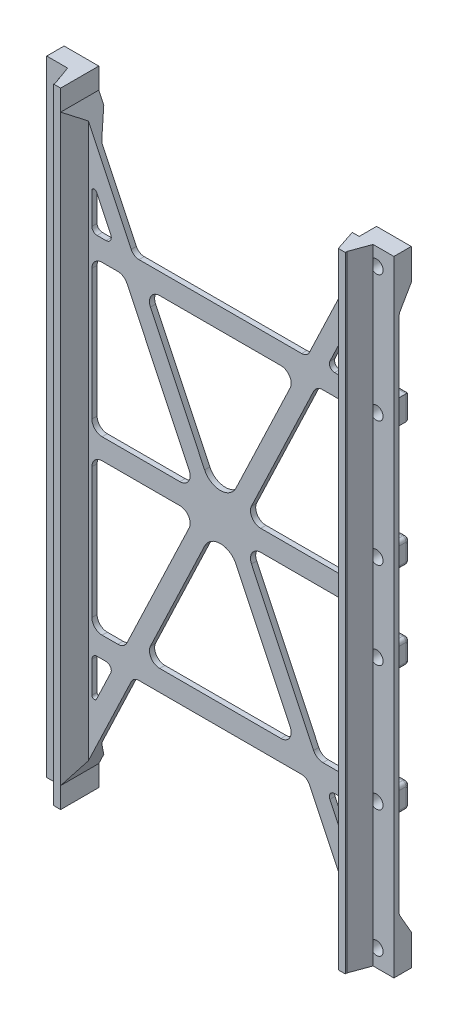
SolidWorks part; units mm, degrees
ref_plane "Front Plane" through (0, 0, 0) normal (0, 0, 1) x (1, 0, 0)
ref_plane "Top Plane" through (0, 0, 0) normal (0, 1, 0) x (1, 0, 0)
ref_plane "Right Plane" through (0, 0, 0) normal (1, 0, 0) x (0, 0, -1)
sketch "Sketch1" plane through (0, 0, 0) normal (0, 0, 1) x (1, 0, 0)
  line L0 (-40, 90) -> (-40, 84)
  line L4 (-50, -90) -> (-50, 90)
  line L5 (-45, 90) -> (-45, -90) construction
  line L6 (-50, -52.5) -> (-30.538, -52.5) construction
  line L7 (-50, 52.5) -> (-30.538, 52.5) construction
  line L8 (-40, 84) -> (-25.6787, 53.9252)
  line L9 (0, 90) -> (0, -90) construction
  line L10 (-50, 0) -> (50, 0) construction
  line L11 (-35.5, 52.5) -> (-32.9136, 52.5)
  line L12 (-40, 90) -> (-50, 90)
  line L13 (-35.668, 63.2731) -> (-31.5593, 54.6449)
  line L14 (-37, -5.95) -> (-37, -43.55)
  line L15 (-34.05, 46.5) -> (-29.5434, 46.5)
  line L16 (-25, 46.5) -> (0, 46.5) construction
  line L17 (-44.5143, 81.8503) -> (-29.5143, 50.3503) construction
  line L18 (-25, 52.5) -> (0, 52.5) construction
  line L19 (-34.05, -3) -> (-11.6387, -3)
  line L20 (-37, 54) -> (-37, 62.9721)
  line L21 (-26.88, 44.8183) -> (-8.9752, 7.2183)
  line L22 (-23.4215, 52.5) -> (23.4215, 52.5)
  line L23 (-40, 84) -> (-25, 52.5) construction
  line L24 (-20.1341, 42.2817) -> (-4.5143, 9.48)
  line L25 (-17.4707, 46.5) -> (17.4707, 46.5)
  line L26 (-17.4707, -46.5) -> (17.4707, -46.5)
  line L27 (-34.05, 3) -> (-11.6387, 3)
  line L28 (-50, 3) -> (50, 3) construction
  line L29 (-37, 5.95) -> (-37, 43.55)
  line L30 (-20.1341, -42.2817) -> (-4.5143, -9.48)
  line L31 (-23.4215, -52.5) -> (23.4215, -52.5)
  line L32 (-26.88, -44.8183) -> (-8.9752, -7.2183)
  line L33 (-37, -54) -> (-37, -62.9721)
  line L34 (-34.05, -46.5) -> (-29.5434, -46.5)
  line L35 (-35.668, -63.2731) -> (-31.5593, -54.6449)
  line L36 (-40, -90) -> (-50, -90)
  line L37 (-35.5, -52.5) -> (-32.9136, -52.5)
  line L38 (-40, -84) -> (-25.6787, -53.9252)
  line L39 (-40, -90) -> (-40, -84)
  line L40 (50, 0) -> (-50, 0) construction
  line L41 (50, 52.5) -> (30.538, 52.5) construction
  line L42 (50, -52.5) -> (30.538, -52.5) construction
  line L43 (45, 90) -> (45, -90) construction
  line L44 (40, -90) -> (40, -84)
  line L45 (40, -84) -> (25.6787, -53.9252)
  line L46 (35.5, -52.5) -> (32.9136, -52.5)
  line L47 (40, -90) -> (50, -90)
  line L48 (35.668, -63.2731) -> (31.5593, -54.6449)
  line L49 (34.05, -46.5) -> (29.5434, -46.5)
  line L50 (37, -54) -> (37, -62.9721)
  line L51 (26.88, -44.8183) -> (8.9752, -7.2183)
  line L52 (20.1341, -42.2817) -> (4.5143, -9.48)
  line L53 (37, 5.95) -> (37, 43.55)
  line L54 (34.05, 3) -> (11.6387, 3)
  line L55 (20.1341, 42.2817) -> (4.5143, 9.48)
  line L56 (26.88, 44.8183) -> (8.9752, 7.2183)
  line L57 (37, 54) -> (37, 62.9721)
  line L58 (34.05, -3) -> (11.6387, -3)
  line L59 (34.05, 46.5) -> (29.5434, 46.5)
  line L60 (37, -5.95) -> (37, -43.55)
  line L61 (35.668, 63.2731) -> (31.5593, 54.6449)
  line L62 (40, 90) -> (50, 90)
  line L63 (35.5, 52.5) -> (32.9136, 52.5)
  line L64 (40, 84) -> (25.6787, 53.9252)
  line L65 (50, -90) -> (50, 90)
  line L66 (40, 90) -> (40, 84)
  arc A0 (-35.668, 63.2731) -> (-37, 62.9721) centre (-36.3, 62.9721) ccw
  arc A1 (-31.5593, 54.6449) -> (-32.9136, 52.5) centre (-32.9136, 54) cw
  arc A2 (-35.5, 52.5) -> (-37, 54) centre (-35.5, 54) cw
  arc A3 (-11.6387, 3) -> (-8.9752, 7.2183) centre (-11.6387, 5.95) ccw
  arc A4 (-34.05, 3) -> (-37, 5.95) centre (-34.05, 5.95) cw
  arc A5 (-26.88, 44.8183) -> (-29.5434, 46.5) centre (-29.5434, 43.55) ccw
  arc A6 (-34.05, 46.5) -> (-37, 43.55) centre (-34.05, 43.55) ccw
  arc A7 (-23.4215, 52.5) -> (-25.6787, 53.9252) centre (-23.4215, 55) cw
  arc A8 (-20.1341, 42.2817) -> (-17.4707, 46.5) centre (-17.4707, 43.55) cw
  circle A9 centre (-45, 85) radius 1.8844
  circle A10 centre (-45, 48.5) radius 1.8844
  circle A11 centre (-45, 12.5) radius 1.8844
  circle A12 centre (-45, -12.5) radius 1.8844
  circle A13 centre (-45, -48.5) radius 1.8844
  circle A14 centre (-45, -85) radius 1.8844
  arc A15 (-20.1341, -42.2817) -> (-17.4707, -46.5) centre (-17.4707, -43.55) ccw
  arc A16 (-23.4215, -52.5) -> (-25.6787, -53.9252) centre (-23.4215, -55) ccw
  arc A17 (-34.05, -46.5) -> (-37, -43.55) centre (-34.05, -43.55) cw
  arc A18 (-26.88, -44.8183) -> (-29.5434, -46.5) centre (-29.5434, -43.55) cw
  arc A19 (-34.05, -3) -> (-37, -5.95) centre (-34.05, -5.95) ccw
  arc A20 (-11.6387, -3) -> (-8.9752, -7.2183) centre (-11.6387, -5.95) cw
  arc A21 (-35.5, -52.5) -> (-37, -54) centre (-35.5, -54) ccw
  arc A22 (-31.5593, -54.6449) -> (-32.9136, -52.5) centre (-32.9136, -54) ccw
  arc A23 (-35.668, -63.2731) -> (-37, -62.9721) centre (-36.3, -62.9721) cw
  arc A24 (35.668, -63.2731) -> (37, -62.9721) centre (36.3, -62.9721) ccw
  arc A25 (31.5593, -54.6449) -> (32.9136, -52.5) centre (32.9136, -54) cw
  arc A26 (35.5, -52.5) -> (37, -54) centre (35.5, -54) cw
  arc A27 (11.6387, -3) -> (8.9752, -7.2183) centre (11.6387, -5.95) ccw
  arc A28 (34.05, -3) -> (37, -5.95) centre (34.05, -5.95) cw
  arc A29 (26.88, -44.8183) -> (29.5434, -46.5) centre (29.5434, -43.55) ccw
  arc A30 (34.05, -46.5) -> (37, -43.55) centre (34.05, -43.55) ccw
  arc A31 (23.4215, -52.5) -> (25.6787, -53.9252) centre (23.4215, -55) cw
  arc A32 (20.1341, -42.2817) -> (17.4707, -46.5) centre (17.4707, -43.55) cw
  circle A33 centre (45, -85) radius 1.8844
  circle A34 centre (45, -48.5) radius 1.8844
  circle A35 centre (45, -12.5) radius 1.8844
  circle A36 centre (45, 12.5) radius 1.8844
  circle A37 centre (45, 48.5) radius 1.8844
  circle A38 centre (45, 85) radius 1.8844
  arc A39 (20.1341, 42.2817) -> (17.4707, 46.5) centre (17.4707, 43.55) ccw
  arc A40 (23.4215, 52.5) -> (25.6787, 53.9252) centre (23.4215, 55) ccw
  arc A41 (34.05, 46.5) -> (37, 43.55) centre (34.05, 43.55) cw
  arc A42 (26.88, 44.8183) -> (29.5434, 46.5) centre (29.5434, 43.55) cw
  arc A43 (34.05, 3) -> (37, 5.95) centre (34.05, 5.95) ccw
  arc A44 (11.6387, 3) -> (8.9752, 7.2183) centre (11.6387, 5.95) cw
  arc A45 (35.5, 52.5) -> (37, 54) centre (35.5, 54) ccw
  arc A46 (31.5593, 54.6449) -> (32.9136, 52.5) centre (32.9136, 54) ccw
  arc A47 (35.668, 63.2731) -> (37, 62.9721) centre (36.3, 62.9721) cw
  arc A48 (4.5143, 9.48) -> (-4.5143, 9.48) centre (0, 11.6297) cw
  arc A49 (4.5143, -9.48) -> (-4.5143, -9.48) centre (0, -11.6297) ccw
  point P0 (0, 0)
  point P37 (-37, 52.5)
  point P51 (-22.1429, 46.5)
  point P60 (-45, 0)
  point P94 (0, -46.5)
  point P98 (-22.1429, -46.5)
  point P99 (-37, -52.5)
  point P175 (0, -52.5)
  point P178 (37, -52.5)
  point P179 (22.1429, -46.5)
  point P180 (45, 0)
  point P181 (22.1429, 46.5)
  point P182 (37, 52.5)
  point P185 (0, 0)
  point P190 (0, 0)
  dimension "D12" = 0.7
  dimension "D13" = 1.5
  dimension "D14" = 2.95
  dimension "D5" = 2.5
  dimension "D15" = 2.95
  dimension "D17" = 5
  dimension "D19" = 77.5
  dimension "D20" = 5
  dimension "D21" = 5
  dimension "D2" = 90
  dimension "D3" = 100
  dimension "D4" = 37.5
  dimension "D6" = 10
  dimension "D8" = 13
  dimension "D10" = 13
  dimension "D16" = 6
  dimension "D18" = 41.5
  dimension "D7" = 5
  dimension "D9" = 6
  dimension "D11" = 3
extrude "Boss-Extrude1" add sketch "Sketch1" along normal blind 1.5
sketch "Sketch2" plane through (50, 0, 0) normal (1, 0, 0) x (0, 0, -1)
  line L0 (0, 90) -> (3.5, 90)
  line L1 (3.5, 90) -> (3.5, 81)
  line L2 (3.5, 81) -> (0.2679, 75.4019)
  line L3 (0, -90) -> (0, 90) construction
  line L4 (0, 74.4019) -> (0, 72.7499)
  line L5 (0, 72.7499) -> (-1.5, 72.7499)
  line L6 (-1.5, -90) -> (-1.5, 90) construction
  line L7 (-1.5, 72.7499) -> (-1.5, 90)
  line L8 (-1.5, 90) -> (0, 90)
  line L9 (14.8391, 0) -> (-20.1791, 0) construction
  line L10 (-1.5, -90) -> (0, -90)
  line L11 (-1.5, -72.7499) -> (-1.5, -90)
  line L12 (0, -72.7499) -> (-1.5, -72.7499)
  line L13 (0, -74.4019) -> (0, -72.7499)
  line L14 (3.5, -81) -> (0.2679, -75.4019)
  line L15 (3.5, -90) -> (3.5, -81)
  line L16 (0, -90) -> (3.5, -90)
  arc A0 (0.2679, 75.4019) -> (0, 74.4019) centre (2, 74.4019) ccw
  arc A1 (0.2679, -75.4019) -> (0, -74.4019) centre (2, -74.4019) cw
  point P10 (0, 74.9378)
  point P27 (0, -74.9378)
  dimension "D4" = 2
  dimension "D1" = 3.5
  dimension "D2" = 9
  dimension "D3" = 150
extrude "Boss-Extrude2" add sketch "Sketch2" against normal blind 28.5
sketch "Sketch3" plane through (0, 0, 0) normal (0, 0, -1) x (-1, 0, 0)
  line L0 (-81.0594, 0) -> (69.2815, 0) construction
  line L1 (-16.8887, -60.7971) -> (-28.951, -60.7971)
  line L3 (-16.8887, -99.7971) -> (-16.8887, -60.7971)
  line L4 (-40, 84) -> (-28.951, 60.7971)
  line L5 (-40, 99.7971) -> (-40, 84)
  line L6 (-40, 99.7971) -> (-16.8887, 99.7971)
  line L7 (-16.8887, 99.7971) -> (-16.8887, 60.7971)
  line L8 (-16.8887, 60.7971) -> (-28.951, 60.7971)
  line L9 (-40, -99.7971) -> (-16.8887, -99.7971)
  line L10 (-40, -99.7971) -> (-40, -84)
  line L11 (-40, -84) -> (-28.951, -60.7971)
  circle A2 centre (-45, 85) radius 1.8844
  circle A3 centre (-45, -85) radius 1.8844
extrude "Cut-Extrude1" cut sketch "Sketch3" against normal through all both and the other way through all
mirror "Mirror1" about plane through (0, 0, 0) normal (1, 0, 0) of "Cut-Extrude1", "Boss-Extrude2"
sketch "Sketch4" plane through (0, 0, 0) normal (0, 0, -1) x (-1, 0, 0)
  line L0 (0, 85.9358) -> (0, 0) construction
  line L1 (-48, 45) -> (-42, 45)
  line L2 (-48, 45) -> (-48, 52)
  line L3 (-48, 52) -> (-42, 52)
  line L4 (-42, 45) -> (-42, 52)
  line L5 (-48, 45) -> (-42, 52) construction
  line L6 (-48, 52) -> (-42, 45) construction
  line L7 (-48, 9) -> (-42, 9)
  line L8 (-48, 9) -> (-48, 16)
  line L9 (-48, 16) -> (-42, 16)
  line L10 (-42, 9) -> (-42, 16)
  line L11 (-48, 9) -> (-42, 16) construction
  line L12 (-48, 16) -> (-42, 9) construction
  line L13 (95.3833, 0) -> (-95.3833, 0) construction
  line L14 (-48, -16) -> (-42, -9) construction
  line L15 (-48, -9) -> (-42, -16) construction
  line L16 (-48, -52) -> (-42, -45) construction
  line L17 (-48, -45) -> (-42, -52) construction
  line L18 (-42, -9) -> (-42, -16)
  line L19 (-48, -16) -> (-42, -16)
  line L20 (-48, -9) -> (-48, -16)
  line L21 (-48, -9) -> (-42, -9)
  line L22 (-42, -45) -> (-42, -52)
  line L23 (-48, -52) -> (-42, -52)
  line L24 (-48, -45) -> (-48, -52)
  line L25 (-48, -45) -> (-42, -45)
  line L26 (48, -45) -> (42, -52) construction
  line L27 (48, -52) -> (42, -45) construction
  line L28 (48, -9) -> (42, -16) construction
  line L29 (48, -16) -> (42, -9) construction
  line L30 (48, 16) -> (42, 9) construction
  line L31 (48, 9) -> (42, 16) construction
  line L32 (48, 52) -> (42, 45) construction
  line L33 (48, 45) -> (42, 52) construction
  line L34 (48, -45) -> (42, -45)
  line L35 (48, -45) -> (48, -52)
  line L36 (48, -52) -> (42, -52)
  line L37 (42, -45) -> (42, -52)
  line L38 (48, -9) -> (42, -9)
  line L39 (48, -9) -> (48, -16)
  line L40 (48, -16) -> (42, -16)
  line L41 (42, -9) -> (42, -16)
  line L42 (42, 9) -> (42, 16)
  line L43 (48, 16) -> (42, 16)
  line L44 (48, 9) -> (48, 16)
  line L45 (48, 9) -> (42, 9)
  line L46 (42, 45) -> (42, 52)
  line L47 (48, 52) -> (42, 52)
  line L48 (48, 45) -> (48, 52)
  line L49 (48, 45) -> (42, 45)
  point P0 (-45, 48.5)
  point P6 (-45, 12.5)
  point P24 (-45, -12.5)
  point P25 (-45, -48.5)
  point P43 (45, -48.5)
  point P44 (45, -12.5)
  point P45 (45, 12.5)
  point P46 (45, 48.5)
  dimension "D1" = 7
  dimension "D2" = 6
  dimension "D3" = 7
  dimension "D4" = 6
extrude "Boss-Extrude3" add sketch "Sketch4" along normal blind 5
sketch "Sketch5" plane through (0, 0, -5) normal (0, 0, -1) x (-1, 0, 0)
  line L0 (0, 69.4636) -> (0, 0) construction
  line L1 (85.5596, 0) -> (-85.5596, 0) construction
  circle A0 centre (-45, 48.5) radius 1.25
  circle A1 centre (-45, 12.5) radius 1.25
  circle A2 centre (-45, -12.5) radius 1.25
  circle A3 centre (-45, -48.5) radius 1.25
  circle A4 centre (-45, 48.5) radius 1.25
  circle A5 centre (-45, 12.5) radius 1.25
  circle A6 centre (-45, -12.5) radius 1.25
  circle A7 centre (-45, -48.5) radius 1.25
  circle A8 centre (45, -48.5) radius 1.25
  circle A9 centre (45, -12.5) radius 1.25
  circle A10 centre (45, 12.5) radius 1.25
  circle A11 centre (45, 48.5) radius 1.25
  circle A12 centre (45, -48.5) radius 1.25
  circle A13 centre (45, -12.5) radius 1.25
  circle A14 centre (45, 12.5) radius 1.25
  circle A15 centre (45, 48.5) radius 1.25
  dimension "D1" = 2.5
  dimension "D2" = 2.5
extrude "Cut-Extrude2" cut sketch "Sketch5" against normal blind 38 contours A2 | A1 | A3 | A8 | A9 | A10 | A11 | A0 region at (45, 48.5, -5) region at (45, 12.5, -5) region at (45, -12.5, -5) region at (45, -48.5, -5) region at (-45, -48.5, -5) region at (-45, -12.5, -5) region at (-45, 12.5, -5) region at (-45, 48.5, -5)
fillet "Fillet1" radius 1 92 edges at (45, 16, 0) (48, -12.5, -5) (48, -12.5, 0) (45, -9, -5) (48, -9, -2.5) (45, -9, 0) (42, 12.5, -5) (42, 16, -2.5) (42, 12.5, 0) (-45, -16, -5) (-45, -16, 0) (-45, 45, -5) (-45, 45, 0) (-45, 9, -5) (-45, 9, 0) (-42, 48.5, -5) (-42, 45, -2.5) (-42, 48.5, 0) (-42, 12.5, -5) (-42, 9, -2.5) (-42, 12.5, 0) (-42, -12.5, -5) (-42, -16, -2.5) (-42, -12.5, 0) (-42, -48.5, -5) (-42, -48.5, 0) (-48, 45, -2.5) (-48, 48.5, -5) (-48, 48.5, 0) (-48, 9, -2.5) (-48, 12.5, -5) (-48, 12.5, 0) (-48, -16, -2.5) (-48, -12.5, -5) (-48, -12.5, 0) (-48, 52, -2.5) (-45, 52, -5) (-42, 52, -2.5) (-45, 52, 0) (-48, 16, -2.5) (-45, 16, -5) (-42, 16, -2.5) (-45, 16, 0) (-48, -9, -2.5) (-45, -9, -5) (-42, -9, -2.5) (-45, -9, 0) (-45, -45, -5) (-42, -45, -2.5) (-45, -45, 0) (-48, -48.5, -5) (-48, -45, -2.5) (-48, -48.5, 0) (-42, -52, -2.5) (-45, -52, -5) (-48, -52, -2.5) (-45, -52, 0) (45, -52, -5) (45, -52, 0) (42, -52, -2.5) (42, -48.5, -5) (42, -48.5, 0) (42, -45, -2.5) (45, -45, -5) (45, -45, 0) (48, -45, -2.5) (48, -48.5, -5) (48, -52, -2.5) (48, -48.5, 0) (48, -16, -2.5) (45, -16, -5) (45, -16, 0) (42, -16, -2.5) (42, -12.5, -5) (42, -9, -2.5) (42, -12.5, 0) (45, 9, -5) (42, 9, -2.5) (45, 9, 0) (48, 16, -2.5) (48, 12.5, -5) (48, 9, -2.5) (48, 12.5, 0) (45, 16, -5) (45, 45, 0) (45, 45, -5) (48, 48.5, -5) (42, 48.5, -5) (45, 52, -5) (45, 52, 0) (42, 48.5, 0) (48, 48.5, 0)
sketch "Sketch6" plane through (0, 0, 1.5) normal (0, 0, 1) x (1, 0, 0)
  circle A0 centre (45, -85) radius 1.8844 construction
  circle A1 centre (45, -48.5) radius 1.8844 construction
  circle A2 centre (45, -12.5) radius 1.8844 construction
  circle A3 centre (45, 12.5) radius 1.8844 construction
  circle A4 centre (45, 48.5) radius 1.8844 construction
  circle A5 centre (45, 85) radius 1.8844 construction
  circle A6 centre (-45, 85) radius 1.8844 construction
  circle A7 centre (-45, 48.5) radius 1.8844 construction
  circle A8 centre (-45, -48.5) radius 1.8844 construction
  circle A9 centre (-45, -12.5) radius 1.8844 construction
  circle A10 centre (-45, 12.5) radius 1.8844 construction
  circle A11 centre (45, -85) radius 1.8844
  circle A12 centre (45, -48.5) radius 1.8844
  circle A13 centre (45, -12.5) radius 1.8844
  circle A14 centre (45, 12.5) radius 1.8844
  circle A15 centre (45, 48.5) radius 1.8844
  circle A16 centre (45, 85) radius 1.8844
  circle A17 centre (-45, 85) radius 1.8844
  circle A18 centre (-45, 48.5) radius 1.8844
  circle A19 centre (-45, -48.5) radius 1.8844
  circle A20 centre (-45, -12.5) radius 1.8844
  circle A21 centre (-45, 12.5) radius 1.8844
extrude "Cut-Extrude3" cut sketch "Sketch6" against normal blind 3
sketch "Sketch7" plane through (0, 0, -3.5) normal (0, 0, -1) x (-1, 0, 0)
  circle A0 centre (45, 85) radius 1.25
  circle A1 centre (-45, 85) radius 1.25
  circle A2 centre (-45, -85) radius 1.25
  circle A3 centre (45, -85) radius 1.25
  circle A4 centre (-45, 85) radius 2.8876
  circle A5 centre (45, 85) radius 2.6855
  circle A6 centre (45, -85) radius 2.715
  circle A7 centre (-45, -85) radius 2.9829
  dimension "D1" = 2.5
  dimension "D2" = 2.5
  dimension "D3" = 2.5
  dimension "D4" = 2.5
extrude "Boss-Extrude4" add sketch "Sketch7" against normal blind 2
sketch "Sketch8" plane through (0, 90, 0) normal (0, 1, 0) x (1, 0, 0)
  line L0 (-50, -1.5) -> (-44, -1.5) construction
  line L1 (-40, -1.5) -> (-50, -1.5) construction
  line L2 (-44, -1.5) -> (-40, -1.5)
  line L3 (-40, -1.5) -> (-40, -7.5) construction
  line L4 (-40, -7.5) -> (-42, -7.5)
  line L5 (-42, -7.5) -> (-42, -6.99)
  line L6 (-44, -1.5) -> (-42, -6.99)
  line L7 (-40, -1.5) -> (-38, -1.5)
  line L8 (-25.6787, -1.5) -> (-40, -1.5) construction
  line L9 (-38, -1.5) -> (-40, -7.5)
  line L10 (0, 20.4834) -> (0, -16.2665) construction
  line L11 (40, -1.5) -> (40, -7.5) construction
  line L12 (50, -1.5) -> (44, -1.5) construction
  line L13 (38, -1.5) -> (40, -7.5)
  line L14 (40, -1.5) -> (38, -1.5)
  line L15 (44, -1.5) -> (42, -6.99)
  line L16 (42, -7.5) -> (42, -6.99)
  line L17 (40, -7.5) -> (42, -7.5)
  line L18 (44, -1.5) -> (40, -1.5)
  dimension "D1" = 6
  dimension "D2" = 4
  dimension "D3" = 6
  dimension "D4" = 2
  dimension "D5" = 0.51
  dimension "D6" = 2
extrude "Boss-Extrude5" add sketch "Sketch8" against normal up to surface (180 mm away) up to face at (-45, -90, -1)
sketch "Sketch9" plane through (0, 0, 1.5) normal (0, 0, -1) x (-1, 0, 0)
  line L2 (-40, 90) -> (-40, 84) construction
  line L5 (-40, 90) -> (-40, 84)
  line L6 (-40, 90) -> (-40, 96.1141)
  line L7 (-40, 96.1141) -> (-31.0572, 96.1141)
  line L8 (-31.0572, 96.1141) -> (-31.0572, 65.2202)
  line L9 (-35.4295, 74.4019) -> (-25.6787, 53.9252) construction
  line L11 (0, 140.4971) -> (0, -140.4971) construction
  line L12 (0, 0) -> (-141.168, 0) construction
  line L20 (-40, 84) -> (-31.0572, 65.2202)
  line L21 (40, 90) -> (40, 84)
  line L22 (-40, 90) -> (-40, 84)
  line L23 (40, 84) -> (31.0572, 65.2202)
  line L24 (31.0572, 96.1141) -> (31.0572, 65.2202)
  line L25 (40, 96.1141) -> (31.0572, 96.1141)
  line L26 (40, 90) -> (40, 96.1141)
  line L27 (40, 90) -> (40, 84)
  line L28 (40, -90) -> (40, -84)
  line L29 (40, -90) -> (40, -96.1141)
  line L30 (40, -96.1141) -> (31.0572, -96.1141)
  line L31 (31.0572, -96.1141) -> (31.0572, -65.2202)
  line L32 (40, -84) -> (31.0572, -65.2202)
  line L33 (40, -90) -> (40, -84)
  line L34 (-40, -90) -> (-40, -84)
  line L35 (-40, -84) -> (-31.0572, -65.2202)
  line L36 (-31.0572, -96.1141) -> (-31.0572, -65.2202)
  line L37 (-40, -96.1141) -> (-31.0572, -96.1141)
  line L38 (-40, -90) -> (-40, -96.1141)
  line L39 (-40, -90) -> (-40, -84)
  line M126 (-38, 79.8) -> (-38, 90)
  line M127 (-38, 90) -> (-40, 90)
extrude "Cut-Extrude4" cut sketch "Sketch9" against normal blind 112 contours L20 L8 L7 L6 M126 M127 | L21 L26 L25 L24 L23 | L28 L32 L31 L30 L29 | L34 L38 L37 L36 L35 region at (34.5065, 84.5701, 1.5) region at (-34.8778, 84.6787, 1.5) region at (-34.8778, -84.6787, 1.5) region at (34.8778, -84.6787, 1.5)
